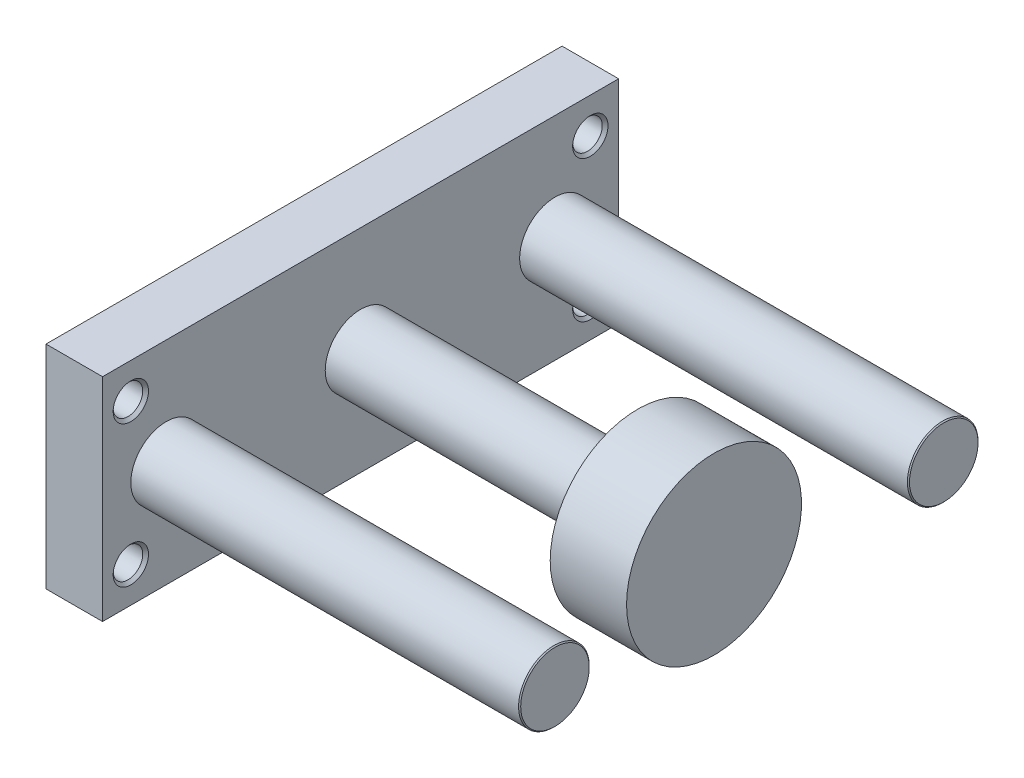
SolidWorks part; units mm, degrees
ref_plane "前视基准面" through (0, 0, 0) normal (0, 0, 1) x (1, 0, 0)
ref_plane "上视基准面" through (0, 0, 0) normal (0, 1, 0) x (1, 0, 0)
ref_plane "右视基准面" through (0, 0, 0) normal (1, 0, 0) x (0, 0, -1)
sketch "草图1" plane through (0, 0, 0) normal (1, 0, 0) x (0, 0, -1)
  line L0 (-73, -30) -> (73, -30)
  line L1 (73, -30) -> (73, 30)
  line L2 (73, 30) -> (-73, 30)
  line L3 (-73, 30) -> (-73, -30)
extrude "凸台-拉伸1" add sketch "草图1" along normal blind 16
ref_plane "基准面1" through (0, 0, 55) normal (0, 0, 1) x (1, 0, 0)
sketch "草图2" plane through (0, 0, 55) normal (0, 0, 1) x (1, 0, 0)
  line L0 (0, 0) -> (0, 9.5)
  line L1 (0, 9.5) -> (0.5, 9)
  line L2 (0.5, 9) -> (6.5, 9)
  line L3 (6.5, 9) -> (6.5, 8)
  line L4 (6.5, 8) -> (1, 8)
  line L5 (1, 8) -> (0.5, 7.5)
  line L6 (0.5, 7.5) -> (0.5, 0)
  line L7 (0.5, 0) -> (0, 0)
  line L8 (6.5, 0) -> (0, 0) construction
revolve "切除-旋转1" cut sketch "草图2" angle 360 about L8 reverse direction yes
sketch "草图3" plane through (0, 0, 0) normal (1, 0, 0) x (0, 0, -1)
  line L0 (-55, 0) -> (55, 0)
pattern_linear "阵列(线性)1" count 3 spacing 55 along (0, 0, -1) of "切除-旋转1"
sketch "草图4" plane through (0, 0, 0) normal (0, 0, 1) x (1, 0, 0)
  line L0 (16, 0) -> (16, 10)
  line L1 (16, 10) -> (94.4, 10)
  line L2 (94.4, 10) -> (94.4, 24.75)
  line L3 (94.4, 24.75) -> (116, 24.75)
  line L4 (116, 24.75) -> (116, 0)
  line L5 (116, 0) -> (16, 0)
  line L6 (116, 0) -> (16, 0) construction
revolve "旋转1" add sketch "草图4" angle 360 about L6 reverse direction yes
ref_plane "基准面2" through (0, 0, 55) normal (0, 0, 1) x (1, 0, 0)
sketch "草图5" plane through (0, 0, 55) normal (0, 0, 1) x (1, 0, 0)
  line L0 (16, 0) -> (16, 10)
  line L1 (16, 10) -> (125.7, 10)
  line L2 (125.7, 10) -> (126, 9.7)
  line L3 (126, 9.7) -> (126, 0)
  line L4 (126, 0) -> (16, 0)
  line L5 (126, 0) -> (16, 0) construction
revolve "旋转2" add sketch "草图5" angle 360 about L5 reverse direction yes
ref_plane "基准面3" through (0, 0, -55) normal (0, 0, 1) x (1, 0, 0)
sketch "草图6" plane through (0, 0, -55) normal (0, 0, 1) x (1, 0, 0)
  line L0 (16, 0) -> (16, 10)
  line L1 (16, 10) -> (125.7, 10)
  line L2 (125.7, 10) -> (126, 9.7)
  line L3 (126, 9.7) -> (126, 0)
  line L4 (126, 0) -> (16, 0)
  line L5 (126, 0) -> (16, 0) construction
revolve "旋转3" add sketch "草图6" angle 360 about L5 reverse direction yes
ref_plane "基准面4" through (0, 0, 65) normal (0, 0, 1) x (1, 0, 0)
sketch "草图7" plane through (0, 0, 65) normal (0, 0, 1) x (1, 0, 0)
  line L0 (0, -20) -> (0, -15)
  line L1 (0, -15) -> (0.812, -15.812)
  line L2 (0.812, -15.812) -> (15.188, -15.812)
  line L3 (15.188, -15.812) -> (16, -15)
  line L4 (16, -15) -> (16, -20)
  line L5 (16, -20) -> (0, -20)
  line L6 (16, -20) -> (0, -20) construction
revolve "切除-旋转2" cut sketch "草图7" angle 360 about L6 reverse direction yes
cosmetic thread "装饰螺纹线1" parameters "D1"=16, "D2"=10
sketch "草图8" plane through (0, 0, 0) normal (1, 0, 0) x (0, 0, -1)
  line L0 (-65, -20) -> (65, -20)
  line L1 (-65, -20) -> (-65, 20)
pattern_linear "阵列(线性)2" count 2 spacing 130 along (0, 0, -1) count 2 spacing 40 along (0, 1, 0) of "切除-旋转2"
ref_plane "基准面5" through (0, 0, 33) normal (0, 0, 1) x (1, 0, 0)
sketch "草图9" plane through (0, 0, 33) normal (0, 0, 1) x (1, 0, 0)
  line L0 (0, 0) -> (0, 2.5)
  line L1 (0, 2.5) -> (8, 2.5)
  line L2 (8, 2.5) -> (8, 0)
  line L3 (8, 0) -> (0, 0)
  line L4 (8, 0) -> (0, 0) construction
revolve "切除-旋转3" cut sketch "草图9" angle 360 about L4 reverse direction yes
ref_plane "基准面6" through (0, 0, -33) normal (0, 0, 1) x (1, 0, 0)
hole_wizard "孔1" positions "草图11" profile "草图10" legacy
sketch "草图11" plane through (0, 0, 0) normal (-1, 0, 0) x (0, 0, 1)
  point P0 (-33, 0)
sketch "草图10" plane through (0, 0, -33) normal (0, 1, 0) x (0, 0, 1)
  line L0 (0, 0) -> (0, 9.4434)
  line L1 (0, 9.4434) -> (2.5, 8)
  line L2 (2.5, 8) -> (2.5, 0)
  line L4 (2.5, 0) -> (0, 0)
  line L6 (0, 9.4434) -> (-2.5, 8) construction
  line L7 (0, -4.2442) -> (0, 117.3081) construction
  dimension "直径" = 5
  dimension "深度" = 8
  dimension "导头角度" = 120
sketch "草图12" plane through (0, 0, 0) normal (1, 0, 0) x (0, 0, -1)
  line L0 (32.7, -2.5) -> (33.3, -2.5)
  line L1 (33.3, 2.5) -> (32.7, 2.5)
  arc A0 (32.7, 2.5) -> (32.7, -2.5) centre (32.7, 0) ccw
  arc A1 (33.3, -2.5) -> (33.3, 2.5) centre (33.3, 0) ccw
extrude "切除-拉伸1" cut sketch "草图12" along normal blind 4
ref_plane "基准面7" through (16, 0, 0) normal (1, 0, 0) x (0, 0, -1)
ref_plane "基准面8" through (6, 0, 0) normal (1, 0, 0) x (0, 0, -1)
ref_plane "for_body XY" through (0, 0, 0) normal (1, 0, 0) x (0, 0, -1)
ref_plane "for_body XZ" through (0, 0, 0) normal (0, -1, 0) x (-1, 0, 0)
ref_plane "for_body YZ" through (0, 0, 0) normal (0, 0, -1) x (-1, 0, 0)
ref_axis "for_body X" through (0, 0, 80.9) along (0, 0, -1)
ref_axis "for_body Y" through (0, -50, 0) along (0, 1, 0)
ref_axis "for_body Z" through (80.9, 0, 0) along (-1, 0, 0)
sketch3d "for_body"
  point P0 (0, 0, 0)
ref_plane "for_rod XY" through (16, 0, 0) normal (-1, 0, 0) x (0, 0, 1)
ref_plane "for_rod XZ" through (0, 0, 0) normal (0, 1, 0) x (1, 0, 0)
ref_plane "for_rod YZ" through (0, 0, 0) normal (0, 0, -1) x (-1, 0, 0)
ref_axis "for_rod X" through (16, 0, 80.9) along (0, 0, -1)
ref_axis "for_rod Y" through (16, 50, 0) along (0, -1, 0)
ref_axis "for_rod Z" through (-80.9, 0, 0) along (1, 0, 0)
sketch3d "for_rod"
  point P0 (16, 0, 0)
ref_plane "screw XY" through (6, 0, 0) normal (-1, 0, 0) x (0, 0, 1)
ref_plane "screw XZ" through (0, 0, 0) normal (0, 1, 0) x (1, 0, 0)
ref_plane "screw YZ" through (0, 0, 0) normal (0, 0, -1) x (-1, 0, 0)
ref_axis "screw X" through (6, 0, 80.9) along (0, 0, -1)
ref_axis "screw Y" through (6, 50, 0) along (0, -1, 0)
ref_axis "screw Z" through (-80.9, 0, 0) along (1, 0, 0)
sketch3d "screw"
  point P0 (6, 0, 0)
